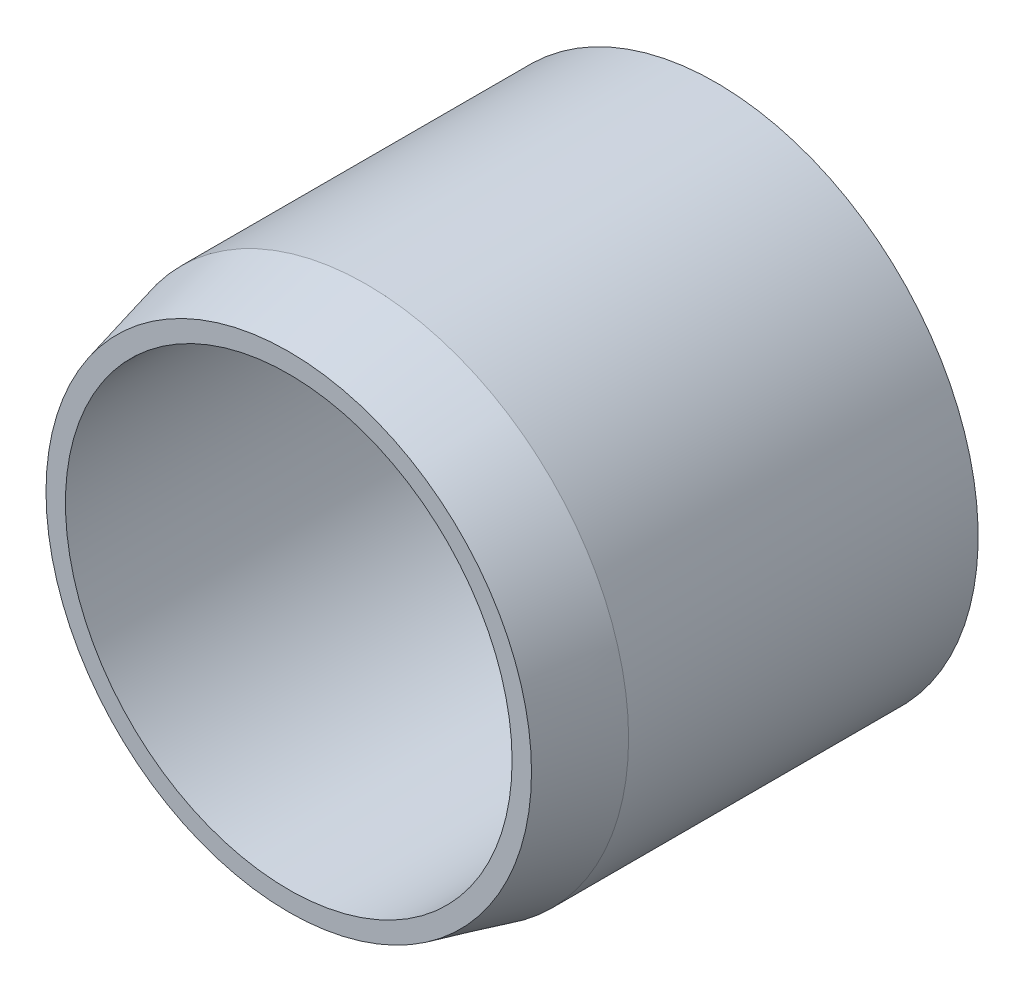
SolidWorks part; units mm, degrees
ref_plane "Front Plane" through (0, 0, 0) normal (0, 0, 1) x (1, 0, 0)
ref_plane "Top Plane" through (0, 0, 0) normal (0, 1, 0) x (1, 0, 0)
ref_plane "Right Plane" through (0, 0, 0) normal (1, 0, 0) x (0, 0, -1)
sketch "Sketch1" plane through (0, 0, 0) normal (0, 0, 1) x (1, 0, 0)
  circle A0 centre (0, 0) radius 13.5
  dimension "D1" = 27
extrude "Extrude-Thin2" add sketch "Sketch1" along normal blind 16 thin thin type one direction reverse wall 2
sketch "Sketch2" plane through (0, 0, 0) normal (0, 0, -1) x (-1, 0, 0)
  circle A0 centre (0, 0) radius 13.5
extrude "Boss-Extrude1" add sketch "Sketch2" along normal blind 2
sketch "Sketch3" plane through (0, 0, 16) normal (0, 0, 1) x (1, 0, 0)
  circle A0 centre (0, 0) radius 11.5
extrude "Extrude-Thin3" add sketch "Sketch3" along normal blind 4 thin thin type one direction wall 1
chamfer "Chamfer1" distance 1 distance2 4 1 edges at (12.5, 0, 16) first distance on face at (13.5, 0, 16)
